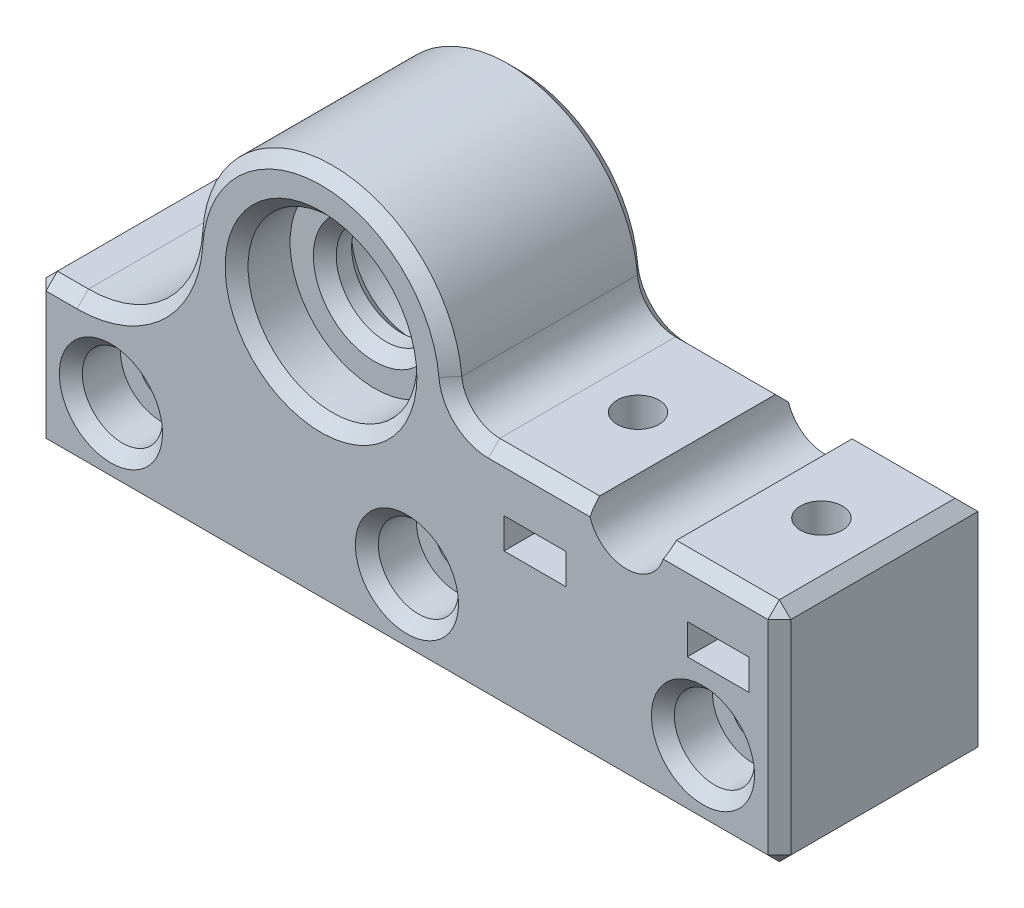
SolidWorks part; units mm, degrees
note: The reader was unsure of these and kept them because the rebuilt part matched: shared geometry of "Sketch1<4>".
material "ABS"
ref_plane "Front Plane" through (0, 0, 0) normal (0, 0, 1) x (1, 0, 0)
ref_plane "Top Plane" through (0, 0, 0) normal (0, 1, 0) x (1, 0, 0)
ref_plane "Right Plane" through (0, 0, 0) normal (1, 0, 0) x (0, 0, -1)
sketch "Sketch1" plane through (0, 0, 0) normal (0, 0, 1) x (1, 0, 0)
  line L0 (0, 0) -> (0, -32.7) construction
  line L1 (-37.5, -32.7) -> (60, -32.7)
  line L2 (-37.5, -32.7) -> (-37.5, -13)
  line L3 (-37.5, -13) -> (60, -13) construction
  line L4 (11.25, -32.7) -> (11.25, 27.5676) construction
  line L7 (60, -23) -> (-37.5, -23) construction
  line L8 (-37.5, -13) -> (-31.9374, -13)
  line L9 (60, -3) -> (45.025, -3)
  line L10 (34.975, -3) -> (21.9089, -3)
  line L11 (60, -3) -> (60, -32.7)
  circle A0 centre (0, 0) radius 11.05
  arc A1 (16.9296, 1.5455) -> (-16.9668, 1.0625) centre (0, 0) ccw
  circle A2 centre (-27.5, -23) radius 2.675
  circle A3 centre (50, -23) radius 2.675
  arc A4 (-31.9374, -13) -> (-16.9668, 1.0625) centre (-31.9374, 2) ccw
  arc A5 (21.9089, -3) -> (16.9296, 1.5455) centre (21.9089, 2) cw
  circle A6 centre (0, 0) radius 6.5
  circle A7 centre (11.25, -23) radius 2.675
  arc A8 (34.975, -3) -> (45.025, -3) centre (40, -3) ccw
  point P4 (0, -22.85)
  dimension "D1" = 22.1
  dimension "D2" = 34
  dimension "D6" = 5.35
  dimension "D7" = 10
  dimension "D9" = 13
  dimension "D10" = 5
  dimension "D11" = 13
  dimension "D3" = 15
  dimension "D5" = 10
  dimension "D12" = 10.05
  dimension "D13" = 40
  dimension "D15" = 20
  dimension "D16" = 19.7
  dimension "D8" = 37.5
  dimension "D4" = 3
extrude "Boss-Extrude1" add sketch "Sketch1" along normal blind 26
extrude "Cut-Extrude2" cut sketch "Sketch1<4>" against normal blind 8 from offset 14 contours A0 A6
sketch "Sketch1<4>" plane through (0, 0, 0) normal (0, 0, 1) x (1, 0, 0) same geometry as "Sketch1"
sketch "Sketch5" plane through (0, 0, 6) normal (0, 0, 1) x (1, 0, 0)
  circle A1 centre (0, 0) radius 11.05
  circle A2 centre (0, 0) radius 11.05
  dimension "D1" = 0
extrude "Cut-Extrude6" cut sketch "Sketch5" against normal up to surface (6 mm away) draft 5
sketch "Sketch4" plane through (0, 0, 26) normal (0, 0, 1) x (1, 0, 0)
  circle A0 centre (-27.5, -23) radius 5.25
  circle A1 centre (50, -23) radius 5.25
  circle A2 centre (11.25, -23) radius 5.25
  dimension "D1" = 10.5
extrude "Cut-Extrude5" cut sketch "Sketch4" against normal blind 6.5
sketch "Sketch9" plane through (0, 0, 26) normal (0, 0, 1) x (1, 0, 0)
  circle A0 centre (0, 0) radius 11.05
  dimension "D1" = 22.1
extrude "Cut-Extrude10" cut sketch "Sketch9" against normal blind 7
chamfer "Chamfer5" distance 1.5 angle 45 26 edges at (-34.7187, -13, 0) (-34.7187, -13, 26) (-0.2422, 16.9983, 0) (-0.2422, 16.9983, 26) (11.25, -32.7, 26) (55.25, -23, 26) (-22.25, -23, 26) (11.5749, 0, 0) (16.5, -23, 26) (-21.6676, -8.933, 0) (-21.6676, -8.933, 26) (6.5, 0, 14) (-37.5, -13, 13) (-37.5, -22.85, 26) (-37.5, -32.7, 13) (28.442, -3, 0) (28.442, -3, 26) (18.5379, -1.6927, 0) (18.5379, -1.6927, 26) (60, -32.7, 13) (52.5125, -3, 0) (60, -3, 13) (52.5125, -3, 26) (60, -17.85, 26) (6.5, 0, 19) (11.05, 0, 26)
sketch "Sketch6" plane through (0, -3, 0) normal (0, 1, 0) x (1, 0, 0)
  line L0 (60, -12.5) -> (21.9089, -12.5) construction
  line L1 (21.9089, -24.5) -> (21.9089, -1.5) construction
  line L2 (21.9089, 0) -> (35.2041, 0) construction
  line L4 (60, 0) -> (60, -24.5) construction
  line L5 (40, 0) -> (40, -26) construction
  line L6 (44.7959, 0) -> (35.2041, 0) construction
  line L7 (35.2041, -26) -> (44.7959, -26) construction
  circle A0 centre (52, -12.5) radius 2.75
  circle A1 centre (28, -12.5) radius 2.75
  dimension "D3" = 5.5
  dimension "D1" = 12.5
  dimension "D2" = 12
extrude "Cut-Extrude7" cut sketch "Sketch6" against normal blind 14
sketch "Sketch7" plane through (0, -3, 0) normal (0, 1, 0) x (1, 0, 0)
  line L0 (23.95, -14.8383) -> (23.95, -26)
  line L1 (28, -17.1765) -> (32.05, -14.8383)
  line L2 (32.05, -14.8383) -> (32.05, -10.1617)
  line L3 (32.05, -10.1617) -> (28, -7.8235)
  line L4 (28, -7.8235) -> (23.95, -10.1617)
  line L5 (23.95, -10.1617) -> (23.95, -14.8383)
  line L6 (23.95, -14.8383) -> (28, -17.1765)
  line L7 (52, -17.1765) -> (56.05, -14.8383)
  line L8 (56.05, -14.8383) -> (56.05, -10.1617)
  line L9 (56.05, -10.1617) -> (52, -7.8235)
  line L10 (52, -7.8235) -> (47.95, -10.1617)
  line L11 (47.95, -10.1617) -> (47.95, -14.8383)
  line L12 (47.95, -14.8383) -> (52, -17.1765)
  line L13 (35.2041, -26) -> (21.9089, -26) construction
  line L14 (23.95, -26) -> (32.05, -26)
  line L15 (32.05, -26) -> (32.05, -14.8383)
  line L16 (47.95, -14.8383) -> (47.95, -26)
  line L17 (58.5, -26) -> (44.7959, -26) construction
  line L18 (47.95, -26) -> (56.05, -26)
  line L19 (56.05, -26) -> (56.05, -14.8383)
  circle A0 centre (28, -12.5) radius 4.05 construction
  circle A1 centre (52, -12.5) radius 4.05 construction
  circle M1 centre (28, -12.5) radius 2.75
  line M3 (21.9089, -24.5) -> (34.975, -24.5)
  dimension "D1" = 8.1
  dimension "D2" = 8.1
extrude "Cut-Extrude8" cut sketch "Sketch7" against normal blind 4 from offset 7 contours L5 L6 L1 L2 L3 L4 M1 | L15 L1 L6 L0 M3 | L11 L12 L7 L8 L9 L10 | L18 L19 L7 L12 L16 | L14 L15 L0 M3
